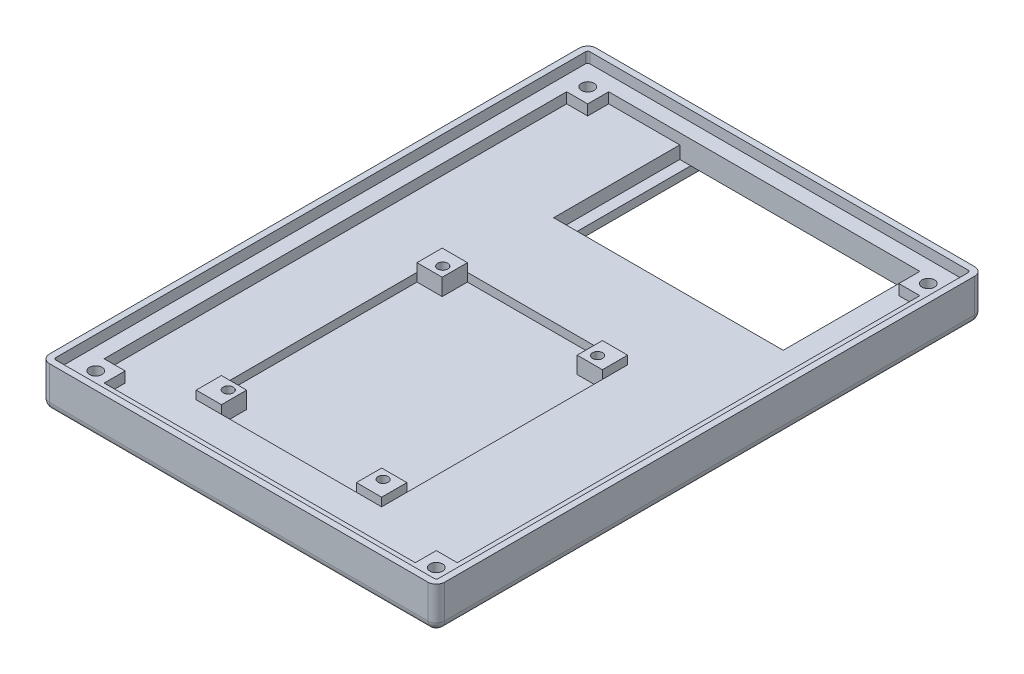
SolidWorks part; units mm, degrees
ref_plane "Front Plane" through (0, 0, 0) normal (0, 0, 1) x (1, 0, 0)
ref_plane "Top Plane" through (0, 0, 0) normal (0, 1, 0) x (1, 0, 0)
ref_plane "Right Plane" through (0, 0, 0) normal (1, 0, 0) x (0, 0, -1)
sketch "Sketch1" plane through (0, 0, 0) normal (0, 1, 0) x (1, 0, 0)
  line L1 (0, 0) -> (94, 0)
  line L2 (0, 0) -> (0, 130)
  line L3 (0, 130) -> (94, 130)
  line L4 (94, 0) -> (94, 130)
  dimension "D1" = 94
  dimension "D2" = 130
extrude "Boss-Extrude1" add sketch "Sketch1" along normal blind 5
sketch "Sketch2" plane through (0, 5, 0) normal (0, 1, 0) x (1, 0, 0)
  line L4 (5, 125) -> (5, 5)
  line L5 (5, 5) -> (89, 5)
  line L6 (89, 5) -> (89, 125)
  line L7 (89, 125) -> (5, 125)
  line L8 (0, 130) -> (0, 0)
  line L9 (0, 0) -> (94, 0)
  line L10 (94, 0) -> (94, 130)
  line L11 (94, 130) -> (0, 130)
  line L12 (0, 130) -> (0, 0)
  line L13 (0, 0) -> (94, 0)
  line L14 (94, 0) -> (94, 130)
  line L15 (94, 130) -> (0, 130)
  dimension "D1" = 0
  dimension "D2" = 5
extrude "Boss-Extrude2" add sketch "Sketch2" along normal blind 5
fillet "Fillet1" radius 2 8 edges at (0, 5, -130) (0, 5, 0) (94, 5, 0) (47, 0, 0) (0, 0, -65) (94, 0, -65) (47, 0, -130) (94, 5, -130)
sketch "Sketch3" plane through (0, 5, 0) normal (0, 1, 0) x (1, 0, 0)
  line L0 (5, 125) -> (5, 5) construction
  line L1 (21.9, 73.5) -> (66, 73.5)
  line L2 (21.9, 73.5) -> (21.9, 15)
  line L3 (21.9, 15) -> (66, 15)
  line L4 (66, 73.5) -> (66, 15)
  line L11 (5, 5) -> (89, 5) construction
  dimension "D1" = 58.5
  dimension "D2" = 44.1
  dimension "D3" = 16.9
  dimension "D4" = 10
extrude "Cut-Extrude1" cut sketch "Sketch3" against normal blind 2
sketch "Sketch5" plane through (0, 3, 0) normal (0, 1, 0) x (1, 0, 0)
  line L0 (66, 73.5) -> (21.9, 73.5) construction
  line L1 (21.9, 73.5) -> (27.9, 73.5)
  line L2 (21.9, 73.5) -> (21.9, 67.5)
  line L3 (21.9, 67.5) -> (27.9, 67.5)
  line L4 (27.9, 73.5) -> (27.9, 67.5)
  line L5 (60, 73.5) -> (66, 73.5)
  line L6 (60, 73.5) -> (60, 67.5)
  line L7 (60, 67.5) -> (66, 67.5)
  line L8 (66, 73.5) -> (66, 67.5)
  line L9 (60, 21) -> (66, 21)
  line L10 (60, 21) -> (60, 15)
  line L11 (60, 15) -> (66, 15)
  line L12 (66, 21) -> (66, 15)
  line L13 (21.9, 21) -> (27.9, 21)
  line L14 (21.9, 21) -> (21.9, 15)
  line L15 (21.9, 15) -> (27.9, 15)
  line L16 (27.9, 21) -> (27.9, 15)
  line L17 (21.9, 73.5) -> (21.9, 15) construction
  line L18 (66, 15) -> (66, 73.5) construction
  line L19 (21.9, 15) -> (66, 15) construction
  dimension "D1" = 6
  dimension "D2" = 6
  dimension "D3" = 6
  dimension "D4" = 6
  dimension "D5" = 6
  dimension "D6" = 6
  dimension "D7" = 6
  dimension "D8" = 6
extrude "Boss-Extrude4" add sketch "Sketch5" along normal blind 4
sketch "Sketch7" plane through (0, 7, 0) normal (0, 1, 0) x (1, 0, 0)
  circle A0 centre (25.6846, 69.839) radius 1.2
  circle A1 centre (62.5146, 69.839) radius 1.2
  circle A2 centre (62.5146, 18.8358) radius 1.2
  circle A3 centre (25.6846, 18.8358) radius 1.2
extrude "Cut-Extrude2" cut sketch "Sketch7" against normal blind 3
sketch "Sketch8" plane through (0, 5, 0) normal (0, 1, 0) x (1, 0, 0)
  line L0 (89, 5) -> (89, 125) construction
  line L1 (26.9, 95) -> (81.5, 95)
  line L2 (26.9, 95) -> (26.9, 125)
  line L3 (26.9, 125) -> (81.5, 125)
  line L4 (81.5, 95) -> (81.5, 125)
  line L6 (89, 125) -> (5, 125) construction
  dimension "D1" = 30
  dimension "D2" = 54.6
  dimension "D3" = 7.5
extrude "Cut-Extrude3" cut sketch "Sketch8" against normal blind 3
sketch "Sketch9" plane through (0, 2, 0) normal (0, 1, 0) x (1, 0, 0)
  line L0 (26.9, 95) -> (81.5, 95) construction
  line L1 (29.5, 96.5) -> (78.9, 96.5)
  line L2 (29.5, 96.5) -> (29.5, 123.5)
  line L3 (29.5, 123.5) -> (78.9, 123.5)
  line L4 (78.9, 96.5) -> (78.9, 123.5)
  line L5 (81.5, 125) -> (26.9, 125) construction
  line L6 (26.9, 125) -> (26.9, 95) construction
  line L8 (89, 5) -> (89, 125) construction
  dimension "D1" = 1.5
  dimension "D2" = 1.5
  dimension "D3" = 2.6
  dimension "D4" = 10.1
extrude "Cut-Extrude4" cut sketch "Sketch9" against normal blind 2
sketch "Sketch10" plane through (0, 0, 0) normal (0, -1, 0) x (1, 0, 0)
  line L1 (78.9, -123.5) -> (29.5, -123.5)
  line L2 (78.9, -123.5) -> (78.9, -130.1195)
  line L3 (78.9, -130.1195) -> (29.5, -130.1195)
  line L4 (29.5, -123.5) -> (29.5, -130.1195)
  line L5 (29.5, -123.5) -> (29.5, -96.5) construction
  line L6 (78.9, -96.5) -> (78.9, -123.5) construction
  line L7 (78.9, -123.5) -> (29.5, -123.5) construction
extrude "Cut-Extrude5" cut sketch "Sketch10" against normal blind 2
sketch "Sketch11" plane through (0, 0, -96.5) normal (0, 0, -1) x (-1, 0, 0)
  line L0 (-29.5, 0) -> (-78.9, 0) construction
  line L1 (-56.7, 1.5) -> (-51.7, 1.5)
  line L2 (-56.7, 1.5) -> (-56.7, 0.5)
  line L3 (-56.7, 0.5) -> (-51.7, 0.5)
  line L4 (-51.7, 1.5) -> (-51.7, 0.5)
  line L5 (-78.9, 0) -> (-78.9, 2) construction
  point P6 (-54.2, 0)
  point P7 (-54.2, 0.5)
  point P10 (-78.9, 1)
  point P11 (-56.7, 1)
  dimension "D1" = 5
  dimension "D2" = 1
extrude "Cut-Extrude6" cut sketch "Sketch11" against normal blind 3
sketch "Sketch14" plane through (0, 10, 0) normal (0, 1, 0) x (1, 0, 0)
  line L8 (89, 5) -> (89, 125)
  line L9 (89, 125) -> (5, 125)
  line L10 (5, 125) -> (5, 5)
  line L11 (5, 5) -> (89, 5)
  line L12 (89, 5) -> (89, 125)
  line L13 (89, 125) -> (5, 125)
  line L14 (5, 125) -> (5, 5)
  line L15 (5, 5) -> (89, 5)
  line L20 (92.5, 2) -> (92.5, 128)
  line L21 (92, 128.5) -> (2, 128.5)
  line L22 (1.5, 128) -> (1.5, 2)
  line L23 (2, 1.5) -> (92, 1.5)
  line L24 (92.5, 2) -> (92.5, 128)
  line L25 (92, 128.5) -> (2, 128.5)
  line L26 (1.5, 128) -> (1.5, 2)
  line L27 (2, 1.5) -> (92, 1.5)
  arc A12 (92.5, 128) -> (92, 128.5) centre (92, 128) ccw
  arc A13 (2, 128.5) -> (1.5, 128) centre (2, 128) ccw
  arc A14 (1.5, 2) -> (2, 1.5) centre (2, 2) ccw
  arc A15 (92, 1.5) -> (92.5, 2) centre (92, 2) ccw
  arc A16 (92.5, 128) -> (92, 128.5) centre (92, 128) ccw
  arc A17 (2, 128.5) -> (1.5, 128) centre (2, 128) ccw
  arc A18 (1.5, 2) -> (2, 1.5) centre (2, 2) ccw
  arc A19 (92, 1.5) -> (92.5, 2) centre (92, 2) ccw
  dimension "D1" = 5
  dimension "D2" = 1.5
extrude "Cut-Extrude8" cut sketch "Sketch14" against normal blind 2.5
sketch "Sketch15" plane through (0, 5, 0) normal (0, 1, 0) x (1, 0, 0)
  line L1 (89, 120) -> (84, 120)
  line L2 (89, 120) -> (89, 125)
  line L3 (89, 125) -> (84, 125)
  line L4 (84, 120) -> (84, 125)
  line L5 (10, 120) -> (5, 120)
  line L6 (10, 120) -> (10, 125)
  line L7 (10, 125) -> (5, 125)
  line L8 (5, 120) -> (5, 125)
  line L9 (10, 5) -> (5, 5)
  line L10 (10, 5) -> (10, 10)
  line L11 (10, 10) -> (5, 10)
  line L12 (5, 5) -> (5, 10)
  line L13 (89, 5) -> (84, 5)
  line L14 (89, 5) -> (89, 10)
  line L15 (89, 10) -> (84, 10)
  line L16 (84, 5) -> (84, 10)
  line L17 (89, 125) -> (81.5, 125) construction
  line L18 (89, 5) -> (89, 125) construction
  line L19 (26.9, 125) -> (5, 125) construction
  line L20 (5, 125) -> (5, 5) construction
  line L22 (5, 5) -> (89, 5) construction
  dimension "D1" = 5
  dimension "D2" = 5
  dimension "D3" = 5
  dimension "D4" = 5
  dimension "D5" = 5
  dimension "D6" = 5
  dimension "D7" = 5
  dimension "D8" = 5
extrude "Boss-Extrude5" add sketch "Sketch15" along normal blind 2.5
sketch "Sketch16" plane through (0, 7.5, 0) normal (0, 1, 0) x (1, 0, 0)
  line L0 (10, 120) -> (10, 125) construction
  line L2 (5, 120) -> (10, 120) construction
  line L4 (84, 125) -> (84, 120) construction
  line L5 (89, 10) -> (84, 10) construction
  circle A0 centre (6.5, 123.5) radius 1.5
  circle A1 centre (87.5, 123.5) radius 1.5
  circle A2 centre (87.5, 6.5) radius 1.5
  circle A3 centre (6.5, 6.5) radius 1.5
  point P0 (6.5, 123.5)
  point P1 (87.5, 123.5)
  point P2 (87.5, 6.5)
  point P3 (6.5, 6.5)
  dimension "D5" = 3
  dimension "D6" = 3
  dimension "D7" = 3
  dimension "D8" = 3
  dimension "D1" = 3.5
  dimension "D2" = 3.5
  dimension "D3" = 3.5
  dimension "D4" = 3.5
extrude "Cut-Extrude9" cut sketch "Sketch16" against normal through all
sketch "Sketch17" plane through (0, 0, 0) normal (0, -1, 0) x (1, 0, 0)
  circle A0 centre (6.5, -6.5) radius 2.8
  circle A1 centre (87.5, -6.5) radius 2.8
  circle A2 centre (87.5, -123.5) radius 2.8
  circle A3 centre (6.5, -123.5) radius 2.8
  dimension "D1" = 5.6
  dimension "D2" = 5.6
  dimension "D3" = 5.6
  dimension "D4" = 5.6
extrude "Cut-Extrude10" cut sketch "Sketch17" against normal blind 3
